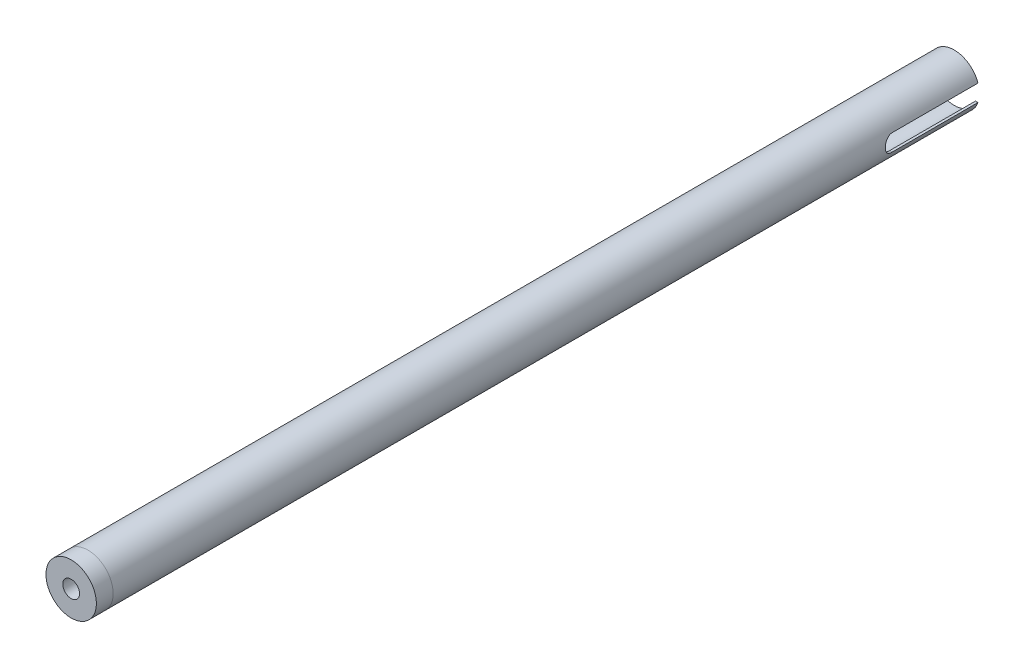
SolidWorks part; units mm, degrees
material "AISI 4130 Steel, normalized at 870C"
ref_plane "Front Plane" through (0, 0, 0) normal (0, 0, 1) x (1, 0, 0)
ref_plane "Top Plane" through (0, 0, 0) normal (0, 1, 0) x (1, 0, 0)
ref_plane "Right Plane" through (0, 0, 0) normal (1, 0, 0) x (0, 0, -1)
sketch "Axis" plane through (0, 0, 0) normal (0, 1, 0) x (1, 0, 0)
  line L0 (0, 0) -> (0, 333.5736) construction
  line L1 (0, 0) -> (0, -21.9075) construction
  line L2 (0, 333.5736) -> (-9.525, 333.5736) construction
  line L3 (0, 368.0751) -> (-10.3188, 330.6984) construction
  dimension "D1" = 21.9075
  dimension "D2" = 9.525
sketch "Sketch1" plane through (0, 0, 0) normal (0, 0, 1) x (1, 0, 0)
  line L0 (-9.525, 0) -> (9.525, 0) construction
  line L1 (-8.9803, 3.175) -> (8.9803, 3.175)
  line L2 (-8.9803, -3.175) -> (8.9803, -3.175)
  circle A0 centre (0, 0) radius 9.525
  circle A1 centre (0, 0) radius 8.636
  circle A2 centre (0, 0) radius 3.175
  dimension "D1" = 19.05
  dimension "D3" = 6.35
  dimension "D2" = 0.889
  dimension "D4" = 6.35
extrude "Threaded insert 1-1" add sketch "Sketch1" against normal blind 6.35 contours A2 L1 A1 | A1 L1 A0 | A2 L0 A1 L1 | A1 L0 A0 L1 | L0 A1 L2 A0 | L0 A2 L2 A1 | A2 L2 A1 | A1 L2 A0 | L0 A1 L2 A2 | L0 A0 L2 A1 | A0 L0 A1 L1 | A1 L0 A2 L1 region at (5.4259, 1.6615, 0) region at (5.4259, -1.6615, 0) region at (8.8881, 1.6046, 0) region at (8.8881, -1.6046, 0) region at (-5.4259, -1.6615, 0) region at (-5.4259, 1.6615, 0) region at (0, 5.4321, 0) region at (0, -5.4321, 0) region at (0, 8.8265, 0) region at (8.5057, -3.3655, 0) region at (-8.8881, -1.6046, 0) region at (-8.8881, 1.6046, 0)
extrude "Threaded insert 1-2" add sketch "Sketch1<3>" against normal blind 6.35 from surface contours A2 L1 A1 | A2 L0 A1 L1 | L0 A2 L2 A1 | A2 L2 A1 | L0 A1 L2 A2 | A1 L0 A2 L1 region at (5.4259, 1.6615, 0) region at (5.4259, -1.6615, 0) region at (-5.4259, -1.6615, 0) region at (-5.4259, 1.6615, 0) region at (0, 5.4321, 0) region at (0, -5.4321, 0) starting at face at (9.525, 0, -6.35)
sketch "Sketch1<3>" plane through (0, 0, 0) normal (0, 0, 1) x (1, 0, 0) same geometry as "Sketch1"
extrude "A-arm tube" add sketch "Sketch1<4>" against normal up to vertex (333.5736 mm away) from surface separate body contours A1 L1 A0 | A1 L0 A0 L1 | L0 A1 L2 A0 | A1 L2 A0 | L0 A0 L2 A1 | A0 L0 A1 L1 region at (8.8881, 1.6046, 0) region at (8.8881, -1.6046, 0) region at (0, 8.8265, 0) region at (8.5057, -3.3655, 0) region at (-8.8881, -1.6046, 0) region at (-8.8881, 1.6046, 0) up to point (0, 0, -333.5736) starting at face at (8.636, 0, -6.35)
sketch "Sketch1<4>" plane through (0, 0, 0) normal (0, 0, 1) x (1, 0, 0) same geometry as "Sketch1"
extrude "Apex slot" cut sketch "Sketch1<5>" along normal blind 35.56 from surface contours A0 L0 A1 L1 | L0 A0 L2 A1 | A1 L0 A0 L1 | L0 A1 L2 A0 region at (8.8881, 1.6046, 0) region at (8.8881, -1.6046, 0) region at (-8.8881, -1.6046, 0) region at (-8.8881, 1.6046, 0) starting at face at (8.636, 0, -333.5736)
sketch "Sketch1<5>" plane through (0, 0, 0) normal (0, 0, 1) x (1, 0, 0) same geometry as "Sketch1"
fillet "Fillet1" radius 3.175 4 edges at (-8.5057, 3.175, -298.0136) (-8.5057, -3.175, -298.0136) (8.5057, -3.175, -298.0136) (8.5057, 3.175, -298.0136)
equation "\"tube diameter\"= 3 / 4"
equation "\"tube thickness\"= .035"
equation "\"apex thickness\"= .25"
equation "\"tube slot\"= 1.4"
equation "\"D1@Sketch1\"=\"tube diameter\""
equation "\"D2@Sketch1\"=\"tube thickness\""
equation "\"threaded insert hole\"= 1 / 4"
equation "\"D3@Sketch1\"=\"threaded insert hole\""
equation "\"D4@Sketch1\"=\"apex thickness\""
equation "\"D1@Apex slot\" = \"tube slot\""
equation "\"D1@Fillet1\"=\"apex thickness\"/2"
equation "\"D2@Axis\"=\"tube diameter\"/2"
